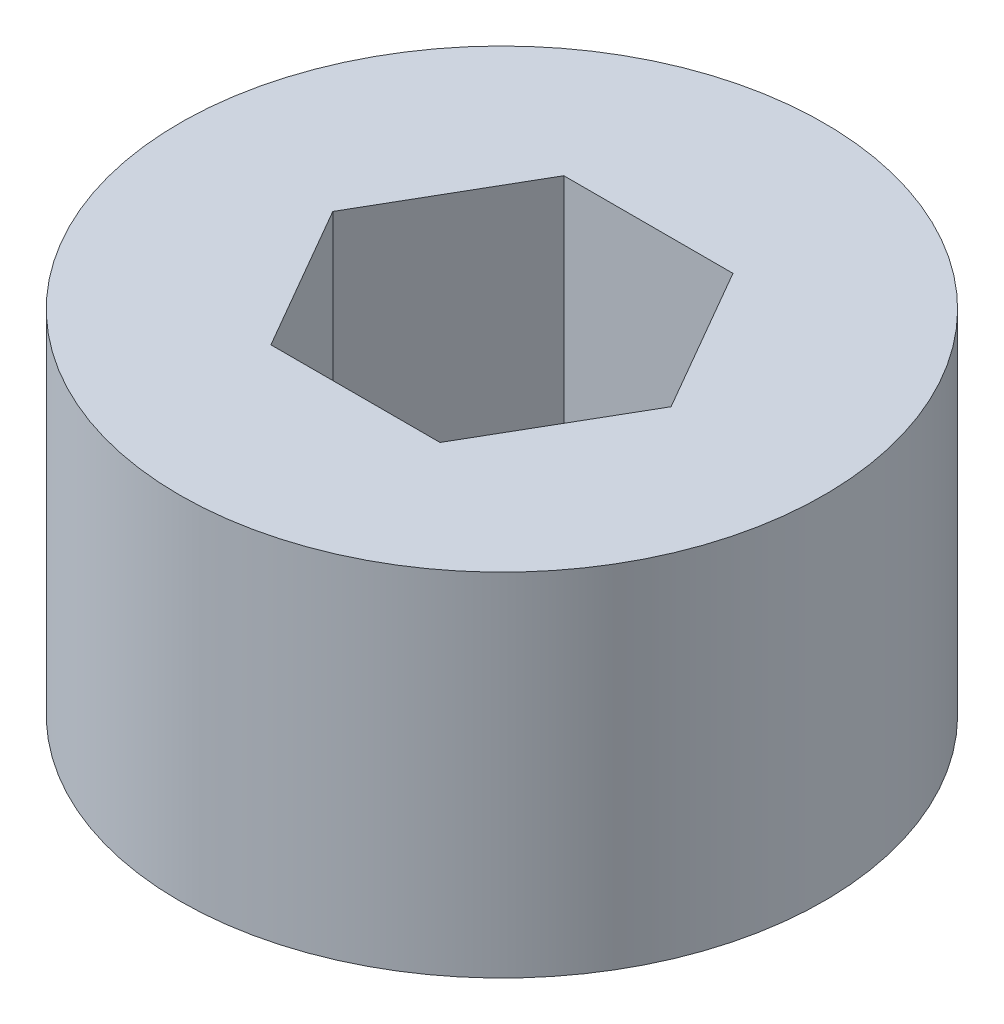
SolidWorks part; units mm, degrees
ref_plane "Front Plane" through (0, 0, 0) normal (0, 0, 1) x (1, 0, 0)
ref_plane "Top Plane" through (0, 0, 0) normal (0, 1, 0) x (1, 0, 0)
ref_plane "Right Plane" through (0, 0, 0) normal (1, 0, 0) x (0, 0, -1)
sketch "Sketch1" plane through (0, 0, 0) normal (0, 1, 0) x (1, 0, 0)
  circle A0 centre (0, 0) radius 2.75
  dimension "D1" = 5.5
extrude "Boss-Extrude1" add sketch "Sketch1" along normal blind 3
sketch "Sketch2" plane through (0, 0, 0) normal (0, 1, 0) x (1, 0, 0)
  line L1 (0.7217, 1.25) -> (-0.7217, 1.25)
  line L2 (-0.7217, 1.25) -> (-1.4434, 0)
  line L3 (-1.4434, 0) -> (-0.7217, -1.25)
  line L4 (-0.7217, -1.25) -> (0.7217, -1.25)
  line L5 (0.7217, -1.25) -> (1.4434, 0)
  line L6 (1.4434, 0) -> (0.7217, 1.25)
  circle A0 centre (0, 0) radius 1.25 construction
  point P1 (0.9588, 1.6606)
  point P10 (1.4434, 0)
  dimension "D1" = 2.5
extrude "Boss-Extrude2" add sketch "Sketch2" along normal blind 3
extrude "Cut-Extrude3" cut sketch "Sketch2<2>" along normal blind 3.9811
sketch "Sketch2<2>" plane through (0, 0, 0) normal (0, 1, 0) x (1, 0, 0) same geometry as "Sketch2"
